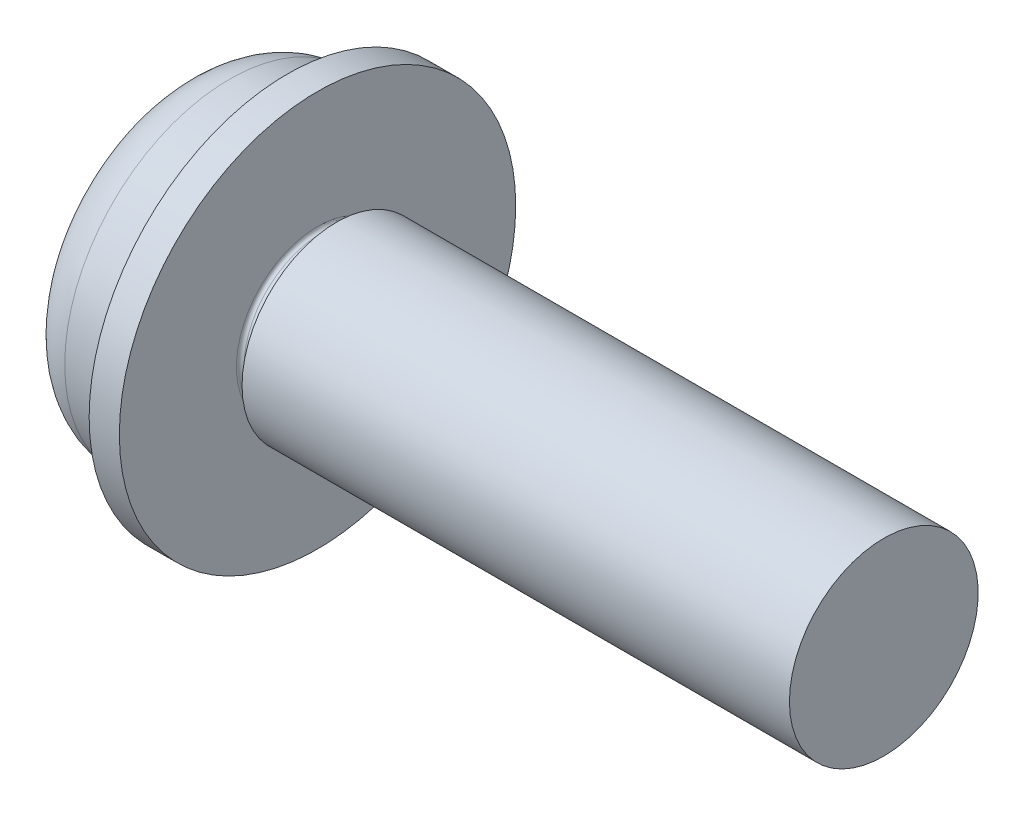
SolidWorks part; units mm, degrees
other "詳細ｱｲﾃﾑ1"
ref_plane "z0" through (0, 0, 0) normal (0, 0, 1) x (1, 0, 0)
ref_plane "y0" through (0, 0, 0) normal (0, 1, 0) x (1, 0, 0)
ref_plane "x0" through (0, 0, 0) normal (1, 0, 0) x (0, 0, -1)
sketch "ｽｹｯﾁ1" plane through (0, 0, 0) normal (0, 0, 1) x (1, 0, 0)
  line L0 (0, 0) -> (30.0467, 0) construction
  line L1 (-2.3304, 4.3661) -> (-0.8, 4.5)
  line L2 (0, 5.25) -> (0, 2.05)
  line L3 (15, 0) -> (-4.1, 0)
  line L4 (0, 2.05) -> (0.5, 2.05)
  line L5 (0.5, 2.05) -> (0.5, 2.5)
  line L6 (0.5, 2.5) -> (15, 2.5)
  line L7 (15, 2.5) -> (15, 0)
  line L8 (0, 5.25) -> (-0.8, 5.25)
  line L9 (-0.8, 5.25) -> (-0.8, 4.5)
  arc A0 (-3.6424, 3.2821) -> (-4.1, 0) centre (7.9, 0) ccw
  arc A1 (-3.6424, 3.2821) -> (-2.3304, 4.3661) centre (-2.1996, 2.8718) cw
  point P16 (-3.3106, 4.2803)
  dimension "D9" = 12
  dimension "D5" = 0.5
  dimension "D7" = 15
  dimension "D3" = 4.1
  dimension "D1" = 0.7894
  dimension "D4" = 5
  dimension "D8" = 85
  dimension "D6" = 4.1
  dimension "D10" = 0.8
  dimension "D11" = 10.5
  dimension "D2" = 9
revolve "ﾍﾞｰｽ -回転" add sketch "ｽｹｯﾁ1" angle 360 about L0
cosmetic thread "ねじ山1" parameters "D2"=4.1
ref_plane "平面4" through (-4.1, 0, 0) normal (1, 0, 0) x (0, 0, -1)
sketch "ｽｹｯﾁ2" plane through (-4.1, 0, 0) normal (1, 0, 0) x (0, 0, -1)
  line L0 (0.515, -2.5) -> (-0.515, -2.5)
  line L1 (0.515, -2.5) -> (0.515, -0.815)
  line L2 (-0.515, 2.5) -> (0.515, 2.5)
  line L3 (-0.515, 2.5) -> (-0.515, 0.815)
  line L4 (2.5, -0.515) -> (0.815, -0.515)
  line L5 (2.5, -0.515) -> (2.5, 0.515)
  line L6 (-2.5, 0.515) -> (-0.815, 0.515)
  line L7 (-2.5, 0.515) -> (-2.5, -0.515)
  line L8 (2.5, 0) -> (-2.5, 0) construction
  line L9 (0, 2.5) -> (0, -2.5) construction
  line L10 (0.815, 0.515) -> (2.5, 0.515)
  line L11 (-0.815, -0.515) -> (-2.5, -0.515)
  line L12 (0.515, 0.815) -> (0.515, 2.5)
  line L13 (-0.515, -0.815) -> (-0.515, -2.5)
  arc A0 (-0.815, 0.515) -> (-0.515, 0.815) centre (-0.815, 0.815) ccw
  arc A1 (0.815, 0.515) -> (0.515, 0.815) centre (0.815, 0.815) cw
  arc A2 (0.515, -0.815) -> (0.815, -0.515) centre (0.815, -0.815) cw
  arc A3 (-0.815, -0.515) -> (-0.515, -0.815) centre (-0.815, -0.815) cw
  point P21 (0.515, 0.515)
  point P26 (-0.515, -0.515)
  dimension "D3" = 0.3
  dimension "D1" = 1.03
  dimension "D2" = 5
extrude "ｶｯﾄ - 押し出し1" cut sketch "ｽｹｯﾁ2" along normal blind 2 draft 5
fillet "ﾌｨﾚｯﾄ1" radius 0.1 1 edges at (0, 0, 2.05)
sketch "ｽｹｯﾁ3" [suppressed] plane through (8, 0, 0) normal (1, 0, 0) x (0, 0, -1)
  circle A0 centre (0, 0) radius 2.5 construction
  circle A1 centre (0, 0) radius 2.5
  circle A2 centre (0, 0) radius 2.05
  dimension "D1" = 4.1
extrude "ｶｯﾄ - 押し出し2" [suppressed] cut sketch "ｽｹｯﾁ3" against normal blind 15
sketch "ｽｹｯﾁ4" plane through (0, 0, 0) normal (1, 0, 0) x (0, 0, -1)
  line L1 (0, 4.6188) -> (-4, 2.3094)
  line L2 (-4, 2.3094) -> (-4, -2.3094)
  line L3 (-4, -2.3094) -> (0, -4.6188)
  line L4 (0, -4.6188) -> (4, -2.3094)
  line L5 (4, -2.3094) -> (4, 2.3094)
  line L6 (4, 2.3094) -> (0, 4.6188)
  circle A0 centre (0, 0) radius 4 construction
  dimension "D1" = 8
extrude "ｶｯﾄ - 押し出し3" [suppressed] cut sketch "ｽｹｯﾁ4" against normal blind 10 from offset 1.5 flip side to cut offset against normal yes
equation "\"D1@ｶｯﾄ - 押し出し2\" = \"D7@ｽｹｯﾁ1\""
equation "\"D1@平面4\" = \"D3@ｽｹｯﾁ1\""
